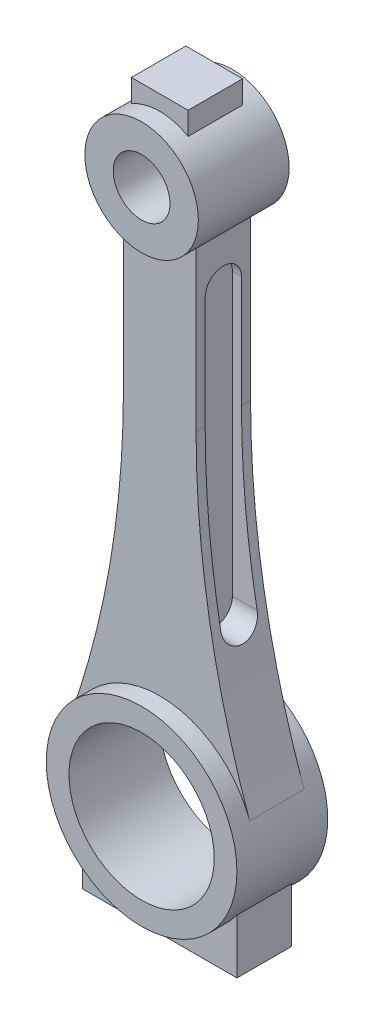
SolidWorks part; units mm, degrees
ref_plane "Front Plane" through (0, 0, 0) normal (0, 0, 1) x (1, 0, 0)
ref_plane "Top Plane" through (0, 0, 0) normal (0, 1, 0) x (1, 0, 0)
ref_plane "Right Plane" through (0, 0, 0) normal (1, 0, 0) x (0, 0, -1)
sketch "Sketch1" plane through (0, 0, 0) normal (0, 0, 1) x (1, 0, 0)
  line L0 (0, 142.7033) -> (0, -24.3288) construction
  line L1 (-8, 75.3953) -> (-8, 110.3953)
  line L2 (8, 75.3953) -> (8, 110.3953)
  line L3 (-6.25, 135.8253) -> (6.25, 135.8253)
  line L4 (-6.25, 135.8253) -> (-6.25, 130.8253)
  line L5 (6.25, 135.8253) -> (6.25, 130.8253)
  line L6 (-17, -24.3288) -> (17, -24.3288)
  line L7 (-17, -24.3288) -> (-17, -12.3288)
  line L8 (17, -24.3288) -> (17, -12.3288)
  circle A0 centre (0, 0) radius 21
  circle A1 centre (0, 0) radius 16
  circle A2 centre (0, 120) radius 12.5
  circle A3 centre (0, 120) radius 6.25
  arc A4 (-8, 75.3953) -> (-19.7874, 7.0327) centre (-212.1328, 75.3953) cw
  arc A5 (8, 75.3953) -> (19.7874, 7.0327) centre (212.1328, 75.3953) ccw
  dimension "D1" = 42
  dimension "D3" = 32
  dimension "D4" = 12.5
  dimension "D5" = 25
  dimension "D2" = 120
  dimension "D6" = 8
  dimension "D7" = 35
  dimension "D8" = 12.5
  dimension "D9" = 5
  dimension "D10" = 34
  dimension "D11" = 12
extrude "Boss-Extrude1" add sketch "Sketch1" along normal mid plane 20 contours A2 L0 A3 | L0 A2 A3 | L0 A0 A1 | A0 L0 A1 region at (3.1629, 131.8041, 0) region at (-0.2795, 129.375, 0) region at (11.8394, 16.7728, 0) region at (-0.4696, 18.5, 0)
extrude "Boss-Extrude2" add sketch "Sketch1<3>" along normal mid plane 12 contours L0 A2 L1 A4 A0 | A2 L0 A0 A5 L2 | L0 L3 L4 A2 | L3 L0 A2 L5 | A0 L0 L6 L8 | L0 A0 L7 L6 region at (3.3472, 133.8599, 0) region at (-3.3472, 133.8599, 0) region at (-5.3967, 57.8448, 0) region at (5.3967, 57.8448, 0) region at (-10.4494, -20.8498, 0) region at (10.4494, -20.8498, 0)
sketch "Sketch1<3>" plane through (0, 0, 0) normal (0, 0, 1) x (1, 0, 0) same geometry as "Sketch1"
sketch "Sketch2" plane through (0, 0, 0) normal (1, 0, 0) x (0, 0, -1)
  line L0 (0, 100) -> (0, 38) construction
  line L1 (4, 100) -> (4, 38)
  line L2 (-4, 100) -> (-4, 38)
  line L3 (10, 107.5) -> (10, 132.5) construction
  arc A0 (4, 100) -> (-4, 100) centre (0, 100) ccw
  arc A1 (-4, 38) -> (4, 38) centre (0, 38) ccw
  point P3 (0, 69)
  dimension "D2" = 4
  dimension "D1" = 62
  dimension "D3" = 100
extrude "Cut-Extrude1" cut sketch "Sketch2" along normal through all from offset 6
mirror "Mirror1" about plane through (0, 0, 0) normal (1, 0, 0) of "Cut-Extrude1"
